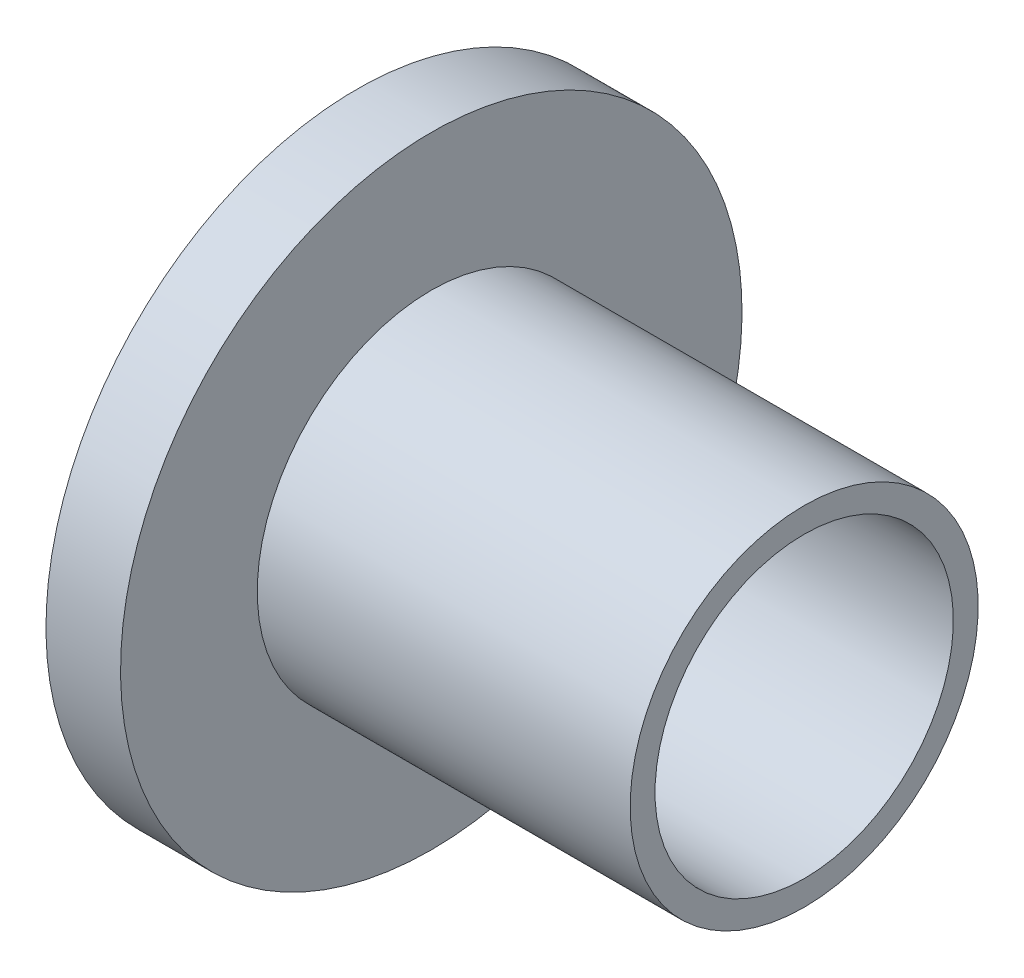
SolidWorks part; units mm, degrees
ref_plane "Front Plane" through (0, 0, 0) normal (0, 0, 1) x (1, 0, 0)
ref_plane "Top Plane" through (0, 0, 0) normal (0, 1, 0) x (1, 0, 0)
ref_plane "Right Plane" through (0, 0, 0) normal (1, 0, 0) x (0, 0, -1)
sketch "Sketch1" plane through (0, 0, 0) normal (0, 0, 1) x (1, 0, 0)
  line L0 (-64.9001, 0) -> (64.9001, 0) construction
  line L1 (-6, 25) -> (-6, 10)
  line L2 (-6, 10) -> (0, 10)
  line L3 (0, 10) -> (0, 12)
  line L4 (0, 12) -> (30, 12)
  line L5 (30, 12) -> (30, 14)
  line L6 (30, 14) -> (0, 14)
  line L7 (0, 14) -> (0, 25)
  line L8 (0, 25) -> (-6, 25)
  point P3 (0, 0)
  point P6 (-3, 25)
  point P13 (0, 0)
  dimension "D1" = 24
  dimension "D2" = 28
  dimension "D3" = 20
  dimension "D4" = 50
  dimension "D5" = 6
  dimension "D6" = 30
revolve "Revolve1" add sketch "Sketch1" angle 360 about L0
